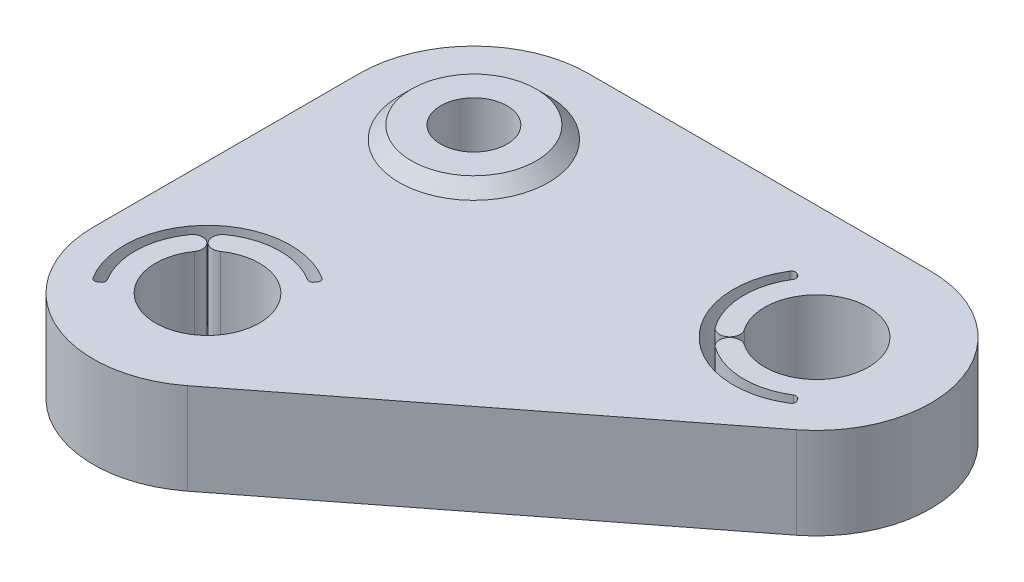
SolidWorks part; units mm, degrees
ref_plane "Front" through (0, 0, 0) normal (0, 0, 1) x (1, 0, 0)
ref_plane "Top" through (0, 0, 0) normal (0, 1, 0) x (1, 0, 0)
ref_plane "Right" through (0, 0, 0) normal (1, 0, 0) x (0, 0, -1)
sketch "Sketch2" plane through (0, 0, 0) normal (0, 1, 0) x (1, 0, 0)
  line L0 (0, 0) -> (0, 12.825) construction
  line L1 (0, 12.825) -> (16.5, 12.825) construction
  line L2 (-5.5, -11.241) -> (32.5382, 18.325) construction
  line L3 (32.5382, 18.325) -> (-5.5, 18.325) construction
  line L4 (-5.5, 18.325) -> (-5.5, -11.241) construction
  line L5 (-5.5, 0) -> (-5.5, 12.825)
  line L6 (0, 18.325) -> (16.5, 18.325)
  line L7 (19.8753, 8.4825) -> (3.3753, -4.3425)
  circle A0 centre (0, 12.825) radius 1.6
  circle A1 centre (16.5, 12.825) radius 2.5
  circle A2 centre (0, 0) radius 2.5
  circle A3 centre (16.5, 12.825) radius 5.5 construction
  circle A4 centre (0, 12.825) radius 5.5 construction
  circle A5 centre (0, 0) radius 5.5 construction
  arc A6 (-5.5, 12.825) -> (0, 18.325) centre (0, 12.825) cw
  arc A7 (16.5, 18.325) -> (19.8753, 8.4825) centre (16.5, 12.825) cw
  arc A8 (3.3753, -4.3425) -> (-5.5, 0) centre (0, 0) cw
  dimension "D3" = 5
  dimension "D4" = 3.2
  dimension "D5" = 3
  dimension "D1" = 12.825
  dimension "D2" = 16.5
extrude "Boss-Extrude1" add sketch "Sketch2" along normal blind 1.57
other "Move Face1" [suppressed] offset 0.0762 parameters "D1"=0.0762
sketch "Sketch3" plane through (0, 1.57, 0) normal (0, 1, 0) x (1, 0, 0)
  line L3 (3.3753, -4.3425) -> (19.8753, 8.4825)
  line L4 (16.5, 18.325) -> (0, 18.325)
  line L5 (-5.5, 12.825) -> (-5.5, 0)
  line L6 (3.3753, -4.3425) -> (19.8753, 8.4825)
  line L7 (16.5, 18.325) -> (0, 18.325)
  line L8 (-5.5, 12.825) -> (-5.5, 0)
  circle A0 centre (0, 0) radius 2.5 construction
  circle A1 centre (16.5, 12.825) radius 2.5 construction
  circle A2 centre (0, 12.825) radius 1.6 construction
  arc A3 (-5.5, 0) -> (3.3753, -4.3425) centre (0, 0) ccw
  arc A4 (19.8753, 8.4825) -> (16.5, 18.325) centre (16.5, 12.825) ccw
  arc A5 (0, 18.325) -> (-5.5, 12.825) centre (0, 12.825) ccw
  arc A6 (-5.5, 0) -> (3.3753, -4.3425) centre (0, 0) ccw
  arc A7 (19.8753, 8.4825) -> (16.5, 18.325) centre (16.5, 12.825) ccw
  arc A8 (0, 18.325) -> (-5.5, 12.825) centre (0, 12.825) ccw
  circle A9 centre (0, 0) radius 2.5
  circle A10 centre (16.5, 12.825) radius 2.5
  circle A11 centre (0, 12.825) radius 1.6
  dimension "D1" = 0
extrude "Boss-Extrude2" add sketch "Sketch3" along normal blind 2.83
sketch "Sketch4" plane through (0, 4.4, 0) normal (0, 1, 0) x (1, 0, 0)
  circle A8 centre (0, 12.825) radius 1.6 construction
  circle A9 centre (0, 12.825) radius 1.6
  circle A10 centre (0, 12.825) radius 3
  dimension "D1" = 6
extrude "Boss-Extrude3" add sketch "Sketch4" along normal blind 0.6
chamfer "Chamfer3" distance 0.6 angle 45 1 edges at (-3, 4.4, -12.825)
sketch "Sketch5" plane through (0, 0, 0) normal (0, -1, 0) x (1, 0, 0)
  line B0 (13.4736, -14.9441) -> (13.3915, -15.0016)
  line B1 (18.6191, -9.7986) -> (18.6766, -9.7165)
  line B2 (14.0425, -11.1043) -> (16.5, -12.825) construction
  arc B3 (13.1072, -14.9437) -> (18.6187, -9.4322) centre (16.5, -12.825) cw
  arc B4 (14.4521, -11.3911) -> (13.633, -10.8175) centre (14.0425, -11.1043) ccw
  arc B5 (13.633, -10.8175) -> (13.5286, -14.6746) centre (16.5, -12.825) ccw
  arc B6 (14.4925, -9.958) -> (18.3496, -9.8536) centre (16.5, -12.825) cw
  arc B7 (15.0661, -10.7771) -> (14.4925, -9.958) centre (14.7793, -10.3675) cw
  arc B8 (14.4521, -11.3911) -> (15.0661, -10.7771) centre (16.5, -12.825) cw
  arc B9 (13.4736, -14.9441) -> (13.5286, -14.6746) centre (13.3589, -14.7803) ccw
  arc B10 (13.3915, -15.0016) -> (13.1072, -14.9437) centre (13.2768, -14.8377) cw
  arc B11 (18.6766, -9.7165) -> (18.6187, -9.4322) centre (18.5127, -9.6018) ccw
  arc B12 (18.6191, -9.7986) -> (18.3496, -9.8536) centre (18.4553, -9.6839) cw
  line B13 (0, 0) -> (-2.8284, -2.8284) construction
  line B14 (2.1191, -3.0264) -> (2.1766, -3.1085)
  line B15 (-3.0264, 2.1191) -> (-3.1085, 2.1766)
  line B16 (-1.7207, -2.4575) -> (0, 0) construction
  arc B17 (2.1187, -3.3928) -> (-3.3928, 2.1187) centre (0, 0) cw
  arc B18 (-1.4339, -2.0479) -> (-2.0075, -2.867) centre (-1.7207, -2.4575) ccw
  arc B19 (-2.0075, -2.867) -> (1.8496, -2.9714) centre (0, 0) ccw
  arc B20 (-2.867, -2.0075) -> (-2.9714, 1.8496) centre (0, 0) cw
  arc B21 (-2.0479, -1.4339) -> (-2.867, -2.0075) centre (-2.4575, -1.7207) cw
  arc B22 (-1.4339, -2.0479) -> (-2.0479, -1.4339) centre (0, 0) cw
  arc B23 (2.1191, -3.0264) -> (1.8496, -2.9714) centre (1.9553, -3.1411) ccw
  arc B24 (2.1766, -3.1085) -> (2.1187, -3.3928) centre (2.0127, -3.2232) cw
  arc B25 (-3.1085, 2.1766) -> (-3.3928, 2.1187) centre (-3.2232, 2.0127) ccw
  arc B26 (-3.0264, 2.1191) -> (-2.9714, 1.8496) centre (-3.1411, 1.9553) cw
sketch_block_instance "5mm_bore_flexure_relief-1"
sketch_block "5mm_bore_flexure_relief" parameters "D4"=2.5, "D6"=0.2, "D1"=80, "D2"=0.5, "D3"=70, "D5"=1
sketch_block_instance "5mm_bore_flexure_relief-2"
extrude "bore relief" cut sketch "Sketch5" against normal through all
sketch "Sketch6" plane through (0, 0, -18.325) normal (0, 0, -1) x (-1, 0, 0)
  line L0 (0, 3.8) -> (-16.5, 3.8) construction
  line L1 (0, 4.4) -> (0, 0) construction
  line L2 (-16.5, 4.4) -> (-16.5, 0) construction
  line L3 (-16.5, 4.4) -> (0, 4.4) construction
  text T0 "RXR-02" font "Century Gothic" height in points 12
  dimension "D1" = 0.6
extrude "Part Num Right" cut sketch "Sketch6" against normal blind 0.4
chamfer "Chamfer2" distance 0.25 angle 60 24 edges at (-2.8284, 0, -2.8284) (-3.2631, 0, 2.2087) (2.2087, 0, -3.2631) (-3.0674, 0, 2.1478) (2.1478, 0, -3.0674) (-2.9452, 0, 1.9953) (1.9953, 0, -2.9452) (-3.4987, 0, -0.0946) (-0.0946, 0, -3.4987) (-2.1707, 0, -2.1303) (-2.1303, 0, -2.1707) (1.7678, 0, 1.7678) (13.6716, 0, -9.9966) (18.7087, 0, -9.5619) (13.2369, 0, -15.0337) (18.6478, 0, -9.7576) (13.4326, 0, -14.9728) (18.4953, 0, -9.8798) (13.5548, 0, -14.8203) (16.4054, 0, -9.3263) (13.0013, 0, -12.7304) (14.3697, 0, -10.6543) (14.3293, 0, -10.6947) (18.2678, 0, -14.5928) first distance on face at (-0.9899, 0, -0.9899)
mirror "Mirror3" [suppressed] of bodies 106 104
delete or keep bodies "Body-Delete/Keep 1" [suppressed] type keep bodies bodies 105
sketch "Sketch7" [suppressed] plane through (0, 0, -18.325) normal (0, 0, -1) x (-1, 0, 0)
  line L0 (27.5, 3.8) -> (11, 3.8) construction
  line L1 (27.5, 4.4) -> (27.5, 0) construction
  line L2 (11, 4.4) -> (11, 0) construction
  line L3 (27.5, 4.4) -> (11, 4.4) construction
  text T0 "LXR-02" font "Century Gothic" height in points 12
  dimension "D1" = 0.6
extrude "Part Num Left" [suppressed] cut sketch "Sketch7" against normal blind 0.4
